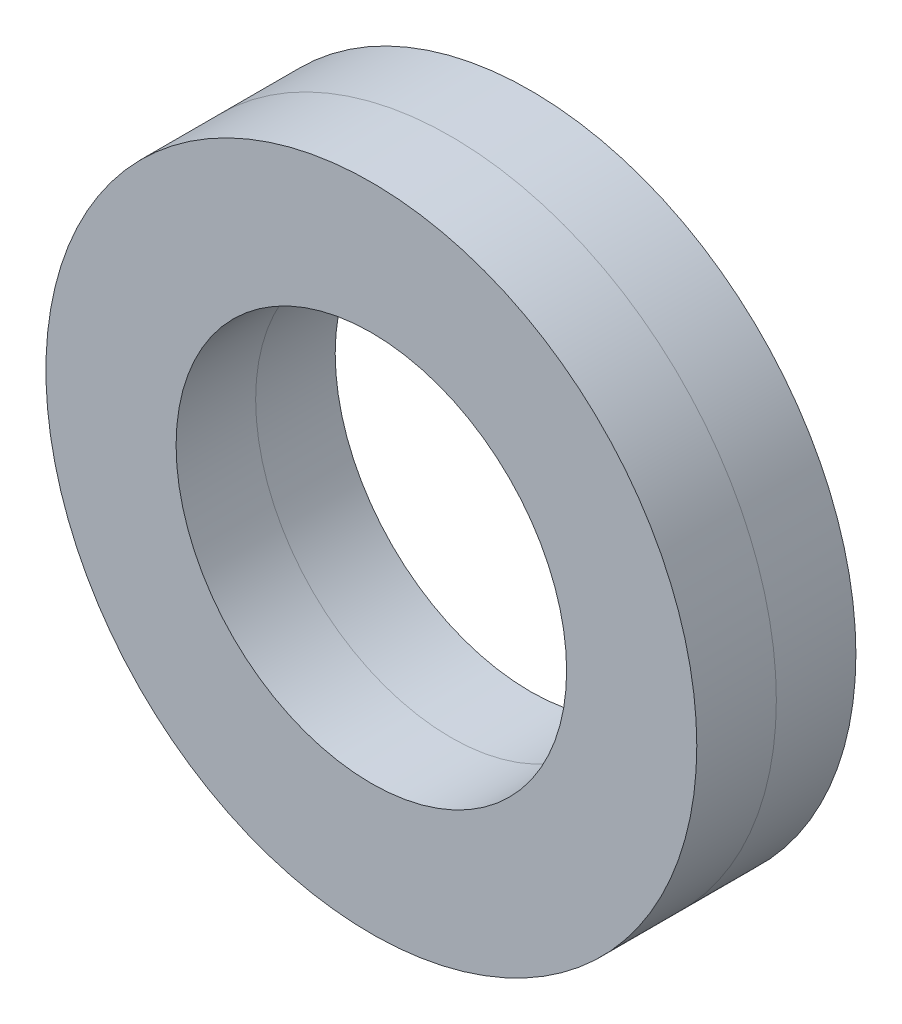
SolidWorks part; units mm, degrees
ref_plane "前视基准面" through (0, 0, 0) normal (0, 0, 1) x (1, 0, 0)
ref_plane "上视基准面" through (0, 0, 0) normal (0, 1, 0) x (1, 0, 0)
ref_plane "右视基准面" through (0, 0, 0) normal (1, 0, 0) x (0, 0, -1)
sketch "草图8" plane through (0, 0, 0) normal (1, 0, 0) x (0, 0, -1)
  line L0 (0, -4.5) -> (0, 4.5)
  line L1 (-1.1, 4.5) -> (1.1, 4.5)
  line L2 (1.1, 4.5) -> (1.1, 2.7)
  line L3 (1.1, 2.7) -> (-1.1, 2.7)
  line L4 (0, 0) -> (1.1754, 0)
  line L5 (-1.1, 4.5) -> (-1.1, 2.7)
  line L6 (-1.1, -4.5) -> (1.1, -4.5)
  line L7 (1.1, -2.7) -> (-1.1, -2.7)
  line L8 (-1.1, 2.7) -> (-1.1, -4.5)
  line L9 (1.1, 2.7) -> (1.1, -4.5)
  point P9 (0, 2.7)
  dimension "D1" = 5.4
  dimension "D2" = 9
  dimension "D3" = 2.2
revolve "旋转3" add sketch "草图8" angle 360 about L4 region at (0, 3.6, 0.55)
revolve "旋转4" add sketch "草图8<8>" angle 360 about L4 region at (0, 3.6, -0.55)
sketch "草图8<8>" plane through (0, 0, 0) normal (1, 0, 0) x (0, 0, -1) same geometry as "草图8"
